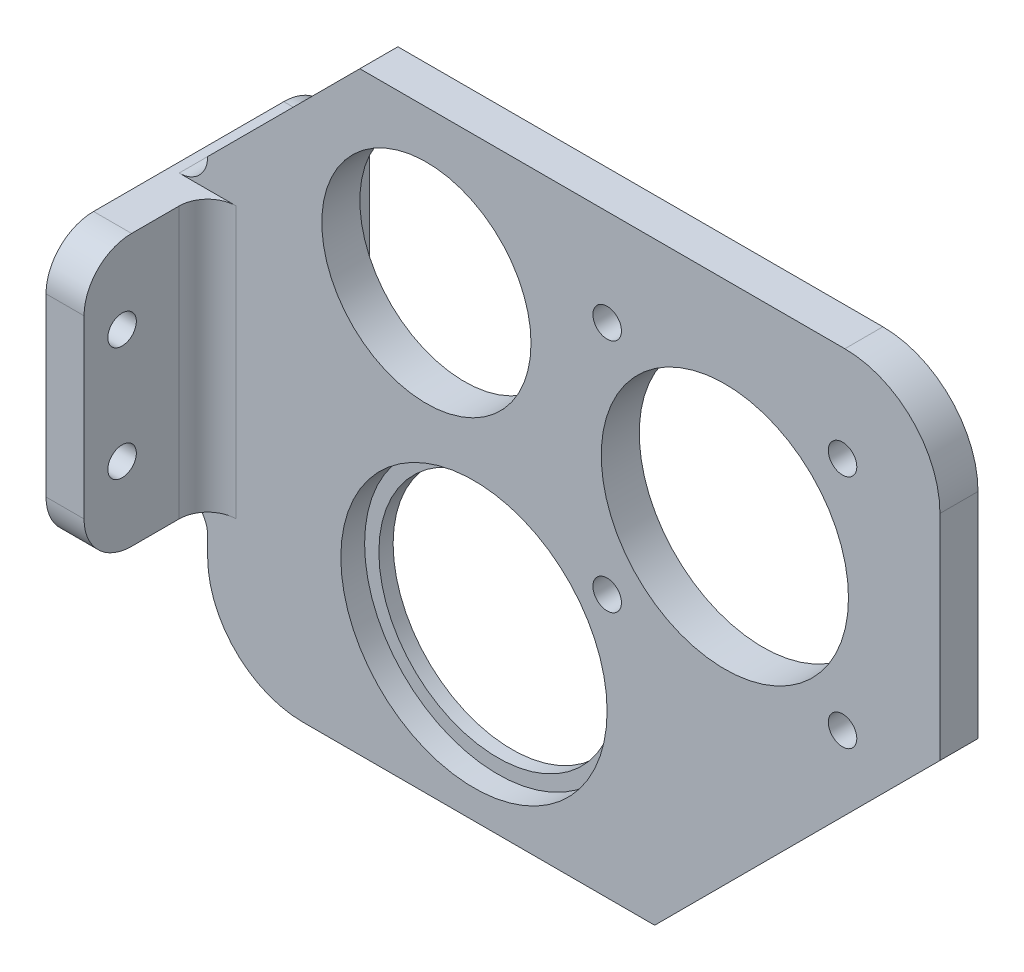
SolidWorks part; units mm, degrees
material "6061 合金"
ref_plane "前视基准面" through (0, 0, 0) normal (0, 0, 1) x (1, 0, 0)
ref_plane "上视基准面" through (0, 0, 0) normal (0, 1, 0) x (1, 0, 0)
ref_plane "右视基准面" through (0, 0, 0) normal (1, 0, 0) x (0, 0, -1)
sketch "草图1" plane through (0, 0, 0) normal (0, 0, 1) x (1, 0, 0)
  line L0 (-52, 26.5) -> (-28, 26.5)
  line L1 (-28, 26.5) -> (-28, -2)
  line L2 (-28, -2) -> (-52, -2)
  line L3 (-52, -2) -> (-52, 2)
  line L4 (-52, 2) -> (-32, 2)
  line L5 (-32, 2) -> (-32, 22.5)
  line L6 (-32, 22.5) -> (-52, 22.5)
  line L7 (-52, 22.5) -> (-52, 26.5)
  line L8 (0, -17) -> (-28, -17) construction
  line L9 (49, 45.5) -> (-28, 45.5)
  line L10 (-28, 45.5) -> (-28, 26.5)
  line L11 (49, 45.5) -> (49, -17)
  line L12 (49, -17) -> (-28, -17)
  line L13 (-28, -17) -> (-28, -2)
  circle A0 centre (0, 0) radius 14
  circle A1 centre (0, 0) radius 17
  circle A2 centre (26.3818, 23) radius 13
  circle A3 centre (26.3818, 23) radius 22.5 construction
  dimension "D1" = 28
  dimension "D2" = 34
  dimension "D3" = 26
  dimension "D4" = 45
  dimension "D14" = 23
  dimension "D6" = 28
  dimension "D5" = 35
  dimension "D7" = 24
  dimension "D8" = 20.5
  dimension "D9" = 28.5
  dimension "D10" = 4
  dimension "D11" = 49
  dimension "D12" = 4
  dimension "D13" = 15
extrude "凸台-拉伸1" add sketch "草图1" along normal blind 4 contours L1 A1 | A1 A0 | A1 A3 | A3 A1 | A3 A2 region at (-11.6808, 11.6808, 0) region at (10.8264, 16.7079, 0)
extrude "凸台-拉伸2" add sketch "草图1<3>" along normal blind 17 and the other way blind 13 contours L7 L6 L5 L4 L3 L2 L1 L0 region at (-40, 26.1274, 0)
sketch "草图1<3>" plane through (0, 0, 0) normal (0, 0, 1) x (1, 0, 0) same geometry as "草图1"
fillet "圆角1" radius 3 2 edges at (-28, 12.25, 0) (-28, 12.25, 4)
sketch "草图4" plane through (0, 0, 17) normal (0, 0, 1) x (1, 0, 0)
  line L0 (-28, -2) -> (-52, -2) construction
  line L1 (-52, 26.5) -> (-32, 26.5)
  line L2 (-52, 26.5) -> (-52, -2)
  line L3 (-52, -2) -> (-32, -2)
  line L4 (-32, 26.5) -> (-32, -2)
  line L5 (-32, 2) -> (-32, 22.5) construction
extrude "切除-拉伸3" cut sketch "草图4" against normal blind 74
sketch "草图9" plane through (0, 0, 4) normal (0, 0, 1) x (1, 0, 0)
  line L0 (26.3818, 23) -> (43.8818, 23) construction
  line L1 (26.3818, 23) -> (38.7562, 35.3744) construction
  circle A0 centre (26.3818, 23) radius 17.5 construction
  circle A1 centre (38.7562, 35.3744) radius 1.5
  circle A2 centre (38.7562, 10.6256) radius 1.5
  circle A3 centre (14.0074, 10.6256) radius 1.5
  circle A4 centre (14.0074, 35.3744) radius 1.5
  point P15 (26.3818, 23)
  dimension "D1" = 35
  dimension "D2" = 3
  dimension "D3" = 45
  dimension "D4" = 4
extrude "切除-拉伸6" cut sketch "草图9" against normal blind 10
sketch "草图10" plane through (-28, 0, 0) normal (1, 0, 0) x (0, 0, -1)
  line L0 (-17, 26.5) -> (-17, -2) construction
  line L2 (-17, 12.25) -> (13, 12.25) construction
  line L3 (13, 26.5) -> (13, -2) construction
  circle A0 centre (-13, 18.25) radius 1.5
  circle A1 centre (-13, 6.25) radius 1.5
  circle A2 centre (9, 18.25) radius 1.5
  circle A3 centre (9, 6.25) radius 1.5
  dimension "D1" = 4
  dimension "D2" = 6
  dimension "D3" = 12
  dimension "D4" = 3
  dimension "D5" = 4
extrude "切除-拉伸7" cut sketch "草图10" against normal blind 10
fillet "圆角2" radius 5 4 edges at (-30, -2, -13) (-30, 26.5, -13) (-30, 26.5, 17) (-30, -2, 17)
sketch "草图11" plane through (0, 0, 4) normal (0, 0, 1) x (1, 0, 0)
  line L0 (-28, 29.5) -> (-28, 45.5)
  line L1 (-28, 45.5) -> (-28, 26.5) construction
  line L2 (-28, 45.5) -> (-12, 45.5)
  line L3 (49, 45.5) -> (-28, 45.5) construction
  line L4 (-12, 45.5) -> (-28, 29.5)
  line L5 (19, -17) -> (49, 13)
  line L6 (49, -17) -> (-28, -17) construction
  line L7 (49, 45.5) -> (49, -17) construction
  line L8 (49, 13) -> (49, -17)
  line L9 (49, -17) -> (19, -17)
  dimension "D1" = 30
  dimension "D2" = 16
extrude "切除-拉伸8" cut sketch "草图11" against normal blind 10
fillet "圆角3" radius 10 2 edges at (49, 45.5, 2) (-28, -17, 2)
fillet "圆角4" radius 3 2 edges at (-28, 26.5, 2) (-28, -2, 2)
sketch "草图13" plane through (0, 0, 0) normal (0, 0, -1) x (-1, 0, 0)
  circle A0 centre (0, 0) radius 12.5
  circle A1 centre (0, 0) radius 14
  dimension "D1" = 25
  dimension "D2" = 28
extrude "凸台-拉伸3" add sketch "草图13" against normal blind 1.5
sketch "草图14" plane through (0, 0, 4) normal (0, 0, 1) x (1, 0, 0)
  line L0 (39, 45.5) -> (-12, 45.5) construction
  line L1 (-32, 3) -> (-32, 21.5) construction
  circle A0 centre (-5, 29.5) radius 11
  dimension "D1" = 22
  dimension "D2" = 16
  dimension "D3" = 27
extrude "切除-拉伸9" cut sketch "草图14" against normal blind 10
